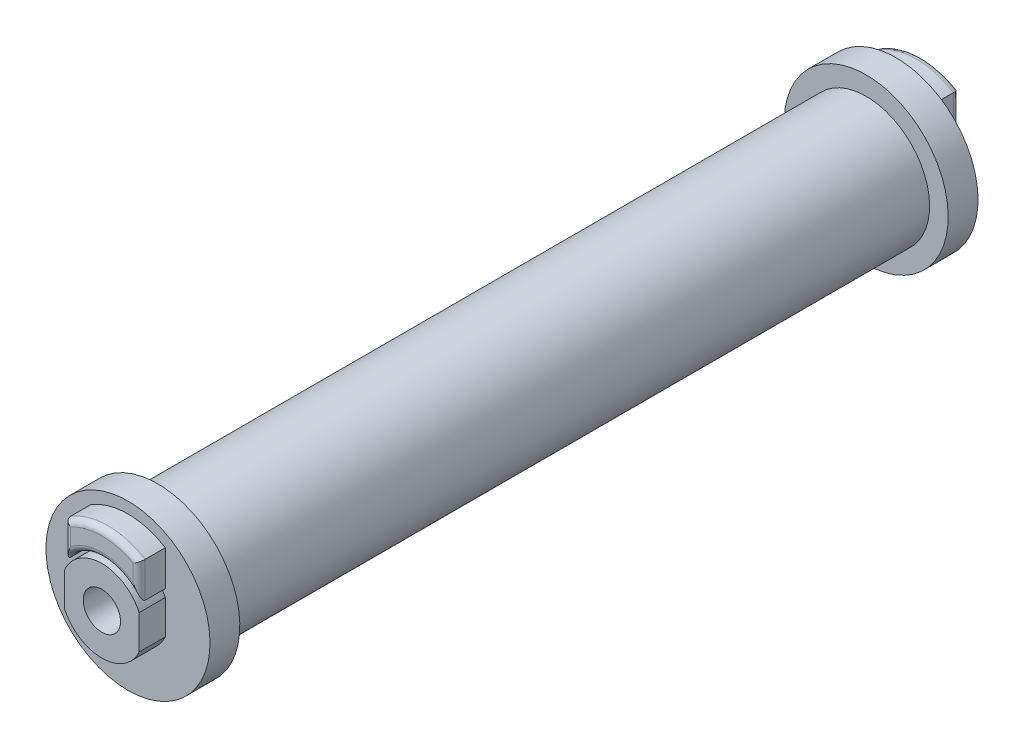
SolidWorks part; units mm, degrees
ref_plane "Alzado" through (0, 0, 0) normal (0, 0, 1) x (1, 0, 0)
ref_plane "Planta" through (0, 0, 0) normal (0, 1, 0) x (1, 0, 0)
ref_plane "Vista lateral" through (0, 0, 0) normal (1, 0, 0) x (0, 0, -1)
sketch "Croquis1" plane through (0, 0, 0) normal (1, 0, 0) x (0, 0, -1)
  line L0 (-58.147, 0) -> (58.147, 0) construction
  line L1 (0, 14.8239) -> (0, -14.8239) construction
  line L2 (0, 2.5) -> (-55, 2.5)
  line L3 (-55, 2.5) -> (-55, 5.5)
  line L4 (-55, 5.5) -> (-51.5, 5.5)
  line L5 (-51.5, 5.5) -> (-51.5, 6)
  line L6 (-51.5, 6) -> (-55, 6)
  line L7 (-55, 6) -> (-55, 9.5)
  line L8 (-55, 9.5) -> (-51.5, 9.5)
  line L9 (-51.5, 9.5) -> (-51.5, 11)
  line L10 (-51.5, 11) -> (-47.5, 11)
  line L11 (-47.5, 11) -> (-47.5, 8.5)
  line L12 (-47.5, 8.5) -> (47.5, 8.5) construction
  line L22 (-47.5, 8.5) -> (0, 8.5)
  line L23 (0, 8.5) -> (0, 2.5)
  point P4 (0, 0)
  point P8 (0, 0)
  point P18 (0, 8.5)
  point P19 (-51.5, 5.75)
  point P21 (-51.5, 10.25)
  point P33 (0, 2.5)
  dimension "D1" = 5
  dimension "D2" = 8.5
  dimension "D3" = 110
  dimension "D4" = 1.5
  dimension "D5" = 11
  dimension "D6" = 3.5
  dimension "D7" = 4
  dimension "D8" = 7.5
  dimension "D9" = 95
  dimension "D10" = 22
revolve "Revolución1" add sketch "Croquis1" angle 360 about L0
sketch "Croquis2" plane through (0, 0, 55) normal (0, 0, 1) x (1, 0, 0)
  line L0 (-12.8857, 0) -> (12.8857, 0) construction
  line L1 (0, 0) -> (0, 9.5) construction
  line L2 (-5, 0) -> (-5, 8.0777)
  line L3 (5, 0) -> (5, 8.0777)
  line L4 (-5, 0) -> (-5, -2.2913)
  line L5 (5, 0) -> (5, -2.2913)
  circle A0 centre (0, 0) radius 9.5 construction
  circle A1 centre (0, 0) radius 5.5 construction
  arc A2 (-5, -2.2913) -> (5, -2.2913) centre (0, 0) ccw
  arc A3 (-5, 8.0777) -> (5, 8.0777) centre (0, 0) ccw
  point P4 (0, 0)
  dimension "D1" = 10
extrude "Cortar-Extruir1" cut sketch "Croquis2" against normal up to surface (3.5 mm away) up to face at (0, -9.5, 51.5)
fillet "Redondeo1" radius 0.8 4 edges at (5, 5.6972, 55) (0, 6, 55) (-5, 5.6972, 55) (0, 9.5, 55)
mirror "Simetría1" about plane through (0, 0, 0) normal (0, 0, 1) of bodies 102
